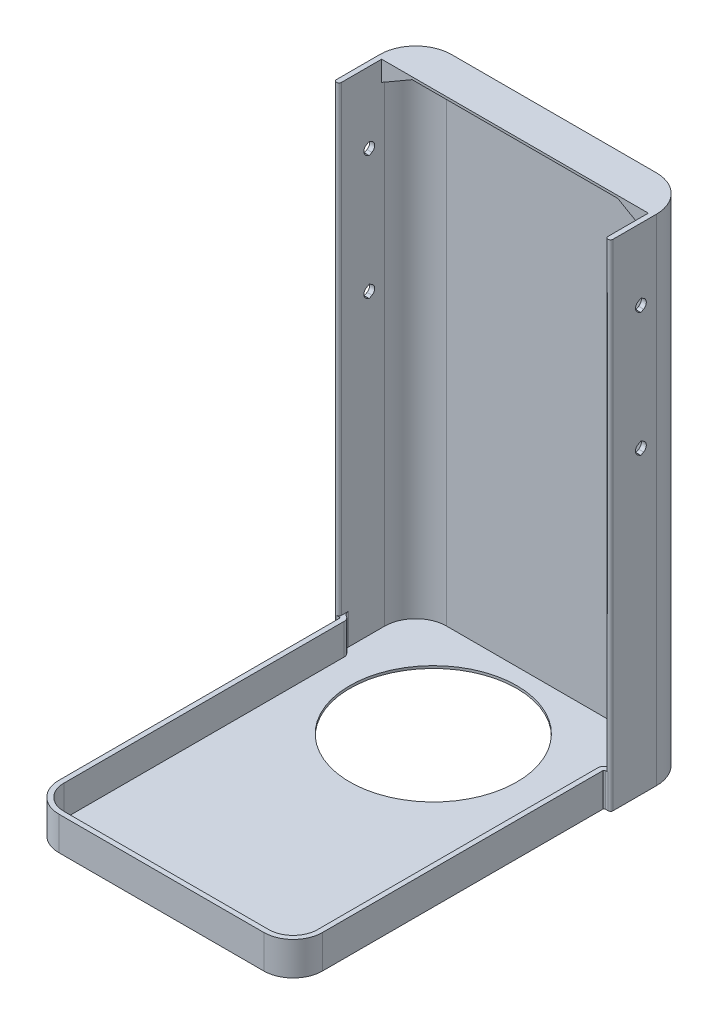
SolidWorks part; units mm, degrees
material "ABS"
ref_plane "Front Plane" through (0, 0, 0) normal (0, 0, 1) x (1, 0, 0)
ref_plane "Top Plane" through (0, 0, 0) normal (0, 1, 0) x (1, 0, 0)
ref_plane "Right Plane" through (0, 0, 0) normal (1, 0, 0) x (0, 0, -1)
sketch "Sketch1" plane through (0, 0, 0) normal (0, 1, 0) x (1, 0, 0)
  line L0 (-33.1, 0) -> (33.1, 0)
  line L1 (-43.1, -10) -> (-43.1, -24)
  line L2 (43.1, -10) -> (43.1, -24)
  line L5 (-43.1, -16.5) -> (43.1, -16.5) construction
  line L6 (-43.1, -13.5) -> (43.1, -13.5) construction
  line L7 (0, -13.5) -> (0, -16.5) construction
  line L9 (44.7, -10) -> (44.7, -24)
  line L10 (-33.1, 1.6) -> (33.1, 1.6)
  line L11 (-44.7, -10) -> (-44.7, -24)
  line L13 (0, -15) -> (0, -11) construction
  line L14 (0, -15) -> (0, -19) construction
  line L15 (44.7, -29) -> (44.7, -45) construction
  line L16 (46.3, -29) -> (46.3, -45) construction
  line L17 (-47.7853, -29.1701) -> (-46.5109, -45.0161) construction
  line L18 (-46.1905, -29.0418) -> (-44.9161, -44.8878) construction
  arc A2 (-33.1, 0) -> (-43.1, -10) centre (-33.1, -10) ccw
  arc A3 (43.1, -10) -> (33.1, 0) centre (33.1, -10) ccw
  arc A8 (44.7, -10) -> (33.1, 1.6) centre (33.1, -10) ccw
  arc A9 (-33.1, 1.6) -> (-44.7, -10) centre (-33.1, -10) ccw
  arc A14 (44.6016, -30.7729) -> (44.7, -29) centre (28.675, -29) cw construction
  arc A15 (46.2377, -30.4806) -> (46.3, -29) centre (28.675, -29) cw construction
  arc A16 (44.7, -24) -> (46.2377, -30.4806) centre (59.125, -24) ccw construction
  arc A17 (43.1, -24) -> (44.6016, -30.7729) centre (59.125, -24) ccw construction
  arc A18 (-43.1, -24) -> (-45.5924, -32.3158) centre (-58.2187, -24) cw construction
  arc A19 (-44.7, -24) -> (-47.3288, -32.0103) centre (-58.2187, -24) cw construction
  arc A20 (-47.3288, -32.0103) -> (-47.7853, -29.1701) centre (-29.644, -27.7111) ccw construction
  arc A21 (-45.5924, -32.3158) -> (-46.1905, -29.0418) centre (-29.644, -27.7111) ccw construction
  arc A22 (-44.7, -24) -> (-43.1, -24) centre (-43.9, -24) ccw
  arc A23 (43.1, -24) -> (44.7, -24) centre (43.9, -24) ccw
  point P25 (0, -15)
  dimension "D3" = 10
  dimension "D1" = 1.6
  dimension "D2" = 86.2
  dimension "D4" = 9
  dimension "D5" = 4
  dimension "D6" = 3
  dimension "D7" = 15
extrude "Boss-Extrude1" add sketch "Sketch1" along normal blind 160
sketch "Sketch2" plane through (0, 160, 0) normal (0, 1, 0) x (1, 0, 0)
  line L0 (44.7, -10) -> (44.7, -24) construction
  line L1 (-33.1, 1.6) -> (33.1, 1.6) construction
  line L2 (-44.7, -10) -> (-44.7, -24) construction
  line L3 (44.7, -10) -> (44.7, -11)
  line L4 (-33.1, 1.6) -> (33.1, 1.6)
  line L5 (-44.7, -10) -> (-44.7, -11)
  line L6 (-44.7, -11) -> (44.7, -11)
  arc A0 (44.7, -10) -> (33.1, 1.6) centre (33.1, -10) ccw construction
  arc A1 (-33.1, 1.6) -> (-44.7, -10) centre (-33.1, -10) ccw construction
  arc A2 (44.7, -10) -> (33.1, 1.6) centre (33.1, -10) ccw
  arc A3 (-33.1, 1.6) -> (-44.7, -10) centre (-33.1, -10) ccw
extrude "Boss-Extrude2" add sketch "Sketch2" against normal blind 0.8
sketch "Sketch3" plane through (44.7, 0, 0) normal (1, 0, 0) x (0, 0, -1)
  line L0 (-19, 160) -> (-11, 160) construction
  line L1 (-24, 160) -> (-10, 160) construction
  line L2 (-15, 160) -> (-15, 137) construction
  line L3 (-15, 137) -> (-15, 97) construction
  line L4 (-15.875, 138.5155) -> (-15, 139.0207)
  line L5 (-15, 139.0207) -> (-14.125, 138.5155)
  line L6 (-15.875, 135.4845) -> (-15, 134.9793)
  line L7 (-15, 134.9793) -> (-14.125, 135.4845)
  line L8 (-15.875, 98.5155) -> (-15, 99.0207)
  line L9 (-15, 99.0207) -> (-14.125, 98.5155)
  line L10 (-14.125, 95.4845) -> (-15, 94.9793)
  line L11 (-15, 94.9793) -> (-15.875, 95.4845)
  arc A0 (-15.875, 138.5155) -> (-15.875, 135.4845) centre (-15, 137) ccw
  arc A1 (-14.125, 135.4845) -> (-14.125, 138.5155) centre (-15, 137) ccw
  arc A2 (-15.875, 98.5155) -> (-15.875, 95.4845) centre (-15, 97) ccw
  arc A3 (-14.125, 95.4845) -> (-14.125, 98.5155) centre (-15, 97) ccw
  dimension "D2" = 1.75
  dimension "D1" = 120
  dimension "D3" = 23
  dimension "D4" = 40
  dimension "D5" = 8
extrude "Cut-Extrude1" cut sketch "Sketch3" against normal through all
sketch "Sketch4" plane through (0, 0, 0) normal (0, -1, 0) x (1, 0, 0)
  line L0 (-43.9, 24.8) -> (-42.6, 24.8)
  line L1 (-42.6, 24.8) -> (-42.6, 115.8)
  line L2 (-33.1, 125.3) -> (33.1, 125.3)
  line L3 (-43.1, 115.8) -> (-43.1, 46.8) construction
  line L5 (42.6, 115.8) -> (42.6, 24.8)
  line L6 (42.6, 24.8) -> (43.9, 24.8)
  line L7 (-43.1, 24) -> (-43.1, 10) construction
  line L8 (-33.1, 0) -> (33.1, 0) construction
  line L9 (43.1, 10) -> (43.1, 24) construction
  line L10 (-43.1, 24) -> (-43.1, 10)
  line L11 (-33.1, 0) -> (33.1, 0)
  line L12 (43.1, 10) -> (43.1, 24)
  arc A0 (-43.1, 24) -> (-44.7, 24) centre (-43.9, 24) ccw construction
  arc A1 (-42.6, 115.8) -> (-33.1, 125.3) centre (-33.1, 115.8) cw
  arc A2 (-33.1, 125.8) -> (-43.1, 115.8) centre (-33.1, 115.8) ccw construction
  arc A3 (33.1, 125.3) -> (42.6, 115.8) centre (33.1, 115.8) cw
  arc A4 (43.1, 115.8) -> (33.1, 125.8) centre (33.1, 115.8) ccw construction
  arc A5 (44.7, 24) -> (43.1, 24) centre (43.9, 24) ccw construction
  arc A6 (-43.1, 10) -> (-33.1, 0) centre (-33.1, 10) ccw construction
  arc A7 (33.1, 0) -> (43.1, 10) centre (33.1, 10) ccw construction
  arc A8 (43.9, 24.8) -> (43.1, 24) centre (43.9, 24) ccw
  arc A9 (-43.1, 24) -> (-43.9, 24.8) centre (-43.9, 24) ccw
  arc A10 (-43.1, 10) -> (-33.1, 0) centre (-33.1, 10) ccw
  arc A11 (33.1, 0) -> (43.1, 10) centre (33.1, 10) ccw
  circle A12 centre (-5.1, 32.3) radius 25 construction
  circle A13 centre (-5.1, 32.3) radius 25 construction
  circle A14 centre (-5.1, 32.3) radius 27
  dimension "D1" = 0.5
  dimension "D2" = 2
extrude "Boss-Extrude3" add sketch "Sketch4" against normal blind 0.8
fillet "Fillet1" radius 0.4 2 edges at (42.6, 0.4, 24.8) (-42.6, 0.4, 24.8)
sketch "Sketch6" plane through (0, 0.8, 0) normal (0, 1, 0) x (1, 0, 0)
  line L0 (-43.1, -23.2) -> (-43, -23.2)
  line L1 (-43.1, -24) -> (-43.1, -11) construction
  line L2 (-41, -25.2) -> (-41, -115.8)
  line L3 (-33.1, -123.7) -> (33.1, -123.7)
  line L4 (41, -115.8) -> (41, -25.2)
  line L5 (43, -23.2) -> (43.1, -23.2)
  line L6 (43.1, -11) -> (43.1, -24) construction
  line L7 (41, -25.2) -> (42.6, -25.2) construction
  line L8 (43.1, -23.2) -> (44.7, -23.2) construction
  line L9 (44.7, -24) -> (44.7, -10) construction
  line L10 (-43, -24.8) -> (-43.9, -24.8) construction
  line L13 (-43.1, -24) -> (-43.1, -10) construction
  line L15 (-42.6, -115.8) -> (-42.6, -25.2) construction
  line L18 (43.1, -10) -> (43.1, -24) construction
  line L19 (43.9, -24.8) -> (43, -24.8) construction
  line L20 (42.6, -25.2) -> (42.6, -115.8) construction
  line L21 (33.1, -125.3) -> (-33.1, -125.3) construction
  line L22 (43.1, -23.2) -> (43.1, -24)
  line L23 (43.9, -24.8) -> (43, -24.8)
  line L24 (42.6, -25.2) -> (42.6, -115.8)
  line L25 (33.1, -125.3) -> (-33.1, -125.3)
  line L26 (-42.6, -115.8) -> (-42.6, -25.2)
  line L27 (-43, -24.8) -> (-43.9, -24.8)
  line L28 (-43.1, -24) -> (-43.1, -23.2)
  arc A0 (-43, -23.2) -> (-41, -25.2) centre (-43, -25.2) cw
  arc A1 (-41, -115.8) -> (-33.1, -123.7) centre (-33.1, -115.8) ccw
  arc A2 (33.1, -123.7) -> (41, -115.8) centre (33.1, -115.8) ccw
  arc A3 (41, -25.2) -> (43, -23.2) centre (43, -25.2) cw
  arc A4 (43, -24.8) -> (42.6, -25.2) centre (43, -25.2) ccw construction
  arc A5 (-42.6, -115.8) -> (-33.1, -125.3) centre (-33.1, -115.8) ccw construction
  arc A6 (33.1, -125.3) -> (42.6, -115.8) centre (33.1, -115.8) ccw construction
  arc A7 (-42.6, -25.2) -> (-43, -24.8) centre (-43, -25.2) ccw construction
  arc A9 (-43.9, -24.8) -> (-43.1, -24) centre (-43.9, -24) ccw construction
  arc A15 (43.1, -24) -> (43.9, -24.8) centre (43.9, -24) ccw construction
  arc A16 (43.1, -24) -> (43.9, -24.8) centre (43.9, -24) ccw
  arc A17 (43, -24.8) -> (42.6, -25.2) centre (43, -25.2) ccw
  arc A18 (33.1, -125.3) -> (42.6, -115.8) centre (33.1, -115.8) ccw
  arc A19 (-42.6, -115.8) -> (-33.1, -125.3) centre (-33.1, -115.8) ccw
  arc A20 (-42.6, -25.2) -> (-43, -24.8) centre (-43, -25.2) ccw
  arc A21 (-43.9, -24.8) -> (-43.1, -24) centre (-43.9, -24) ccw
extrude "Boss-Extrude4" add sketch "Sketch6" along normal blind 10
fillet "Fillet2" radius 2 2 edges at (43.1, 5.8, 23.2) (-43.1, 5.8, 23.2)
chamfer "Chamfer1" distance 5.7 angle 60 5 edges at (-43.1, 159.2, 10.5) (43.1, 159.2, 10.5) (-40.1711, 159.2, 2.9289) (40.1711, 159.2, 2.9289) (0, 159.2, 0) first distance on face at (-43.1, 137, 15) first distance on face at (43.1, 137, 15) first distance on face at (-39.1355, 80, 3.9645) first distance on face at (39.1355, 80, 3.9645) first distance on face at (0, 80, 0)
